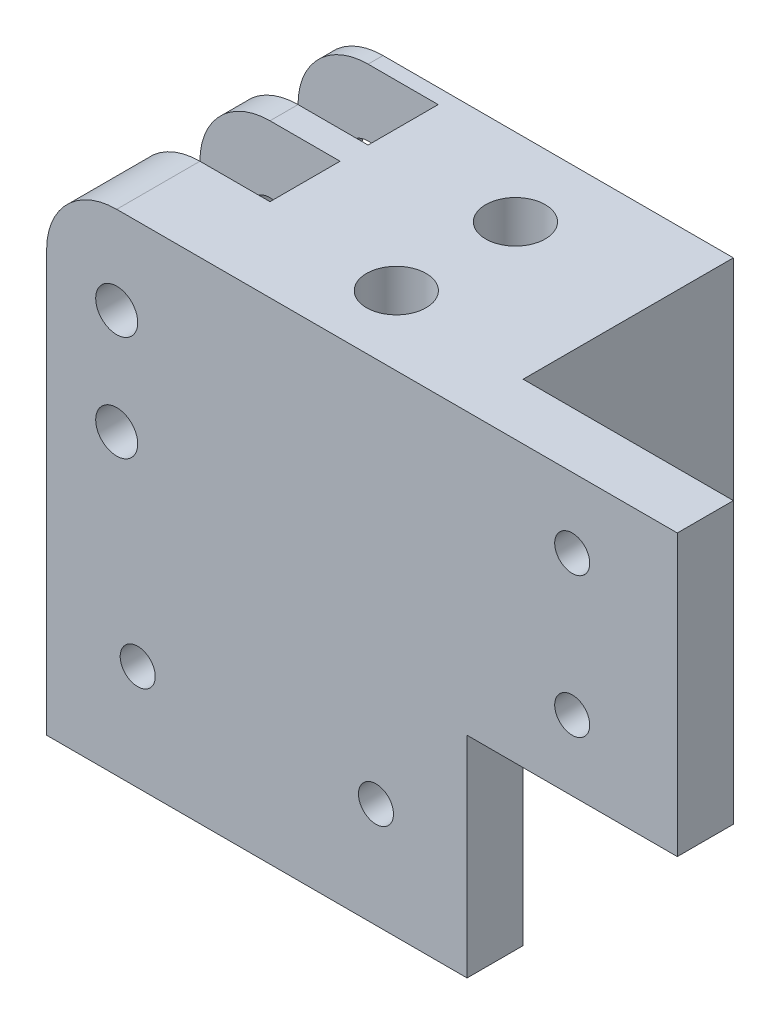
SolidWorks part; units mm, degrees
ref_plane "Front Plane" through (0, 0, 0) normal (0, 0, 1) x (1, 0, 0)
ref_plane "Top Plane" through (0, 0, 0) normal (0, 1, 0) x (1, 0, 0)
ref_plane "Right Plane" through (0, 0, 0) normal (1, 0, 0) x (0, 0, -1)
sketch "Esboço1" plane through (0, 0, 0) normal (0, 0, 1) x (1, 0, 0)
  line L0 (440, 72.2122) -> (440, 102.2122) construction
  line L1 (440, 72.2122) -> (380, 72.2122)
  line L2 (470, 102.2122) -> (470, 142.2122)
  line L3 (470, 142.2122) -> (390, 142.2122)
  line L4 (380, 72.2122) -> (380, 132.2122)
  line L5 (440, 102.2122) -> (470, 102.2122) construction
  line L6 (440, 72.2122) -> (440, 102.2122)
  line L7 (440, 102.2122) -> (470, 102.2122)
  line L9 (440, 87.2122) -> (380, 87.2122) construction
  line L10 (455, 102.2122) -> (455, 142.2122) construction
  arc A0 (390, 142.2122) -> (380, 132.2122) centre (390, 132.2122) ccw
  dimension "D1" = 10
  dimension "D2" = 40
  dimension "D3" = 60
extrude "Ressalto-extrusão1" add sketch "Esboço1" along normal blind 8 contours L4 A0 L3 L2 L7 L6 L1
hole_wizard "Broca de rosquear para tarraxa de M6x1.01" positions "Esboço2" profile "Esboço3" hole size "M6x1.0" standard "Ansi Metric" end condition through all
sketch "Esboço2" plane through (0, 0, 8) normal (0, 0, 1) x (1, 0, 0)
  line L0 (440, 87.2122) -> (380, 87.2122) construction
  line L1 (455, 102.2122) -> (455, 142.2122) construction
  line L2 (380, 72.2122) -> (380, 132.2122) construction
  line L3 (440, 72.2122) -> (440, 102.2122) construction
  line L4 (470, 142.2122) -> (390, 142.2122) construction
  point P0 (393, 87.2122)
  point P4 (427, 87.2122)
  point P6 (455, 112.2122)
  point P10 (455, 132.2122)
  dimension "D1" = 13
  dimension "D2" = 13
  dimension "D3" = 10
  dimension "D4" = 10
sketch "Esboço3" plane through (393, 87.2122, 8) normal (1, 0, 0) x (0, -1, 0)
  line L0 (0, 0) -> (0, 8)
  line L1 (0, 8) -> (2.5, 8)
  line L2 (2.5, 8) -> (2.5, 0)
  line L5 (2.5, 0) -> (0, 0)
  line L11 (0, -6.35) -> (0, 107.95) construction
  dimension "Thru Hole Dia." = 5
  dimension "Thru Hole Depth" = 8
sketch "Esboço4" plane through (0, 0, 0) normal (0, 0, -1) x (-1, 0, 0)
  line L0 (-470, 142.2122) -> (-390, 142.2122) construction
  line L1 (-390, 142.2122) -> (-440, 142.2122)
  line L2 (-380, 132.2122) -> (-380, 102.2122)
  line L3 (-380, 102.2122) -> (-440, 102.2122)
  line L4 (-440, 142.2122) -> (-440, 102.2122)
  line L5 (-380, 72.2122) -> (-380, 132.2122) construction
  arc A0 (-390, 142.2122) -> (-380, 132.2122) centre (-390, 132.2122) cw
  point P11 (-380, 142.2122)
  dimension "D1" = 10
extrude "Ressalto-extrusão2" add sketch "Esboço4" along normal blind 30
sketch "Esboço6" plane through (380, 0, 0) normal (-1, 0, 0) x (0, 0, 1)
  line L0 (-30, 142.2122) -> (0, 142.2122) construction
  line L1 (-27.8749, 102.2122) -> (-17.8749, 102.2122)
  line L2 (-27.8749, 102.2122) -> (-27.8749, 142.2122)
  line L3 (-27.8749, 142.2122) -> (-17.8749, 142.2122)
  line L4 (-17.8749, 102.2122) -> (-17.8749, 142.2122)
  line L5 (-13.8749, 117.2122) -> (-3.8749, 117.2122)
  line L6 (-13.8749, 117.2122) -> (-13.8749, 142.2122)
  line L7 (-13.8749, 142.2122) -> (-3.8749, 142.2122)
  line L8 (-3.8749, 117.2122) -> (-3.8749, 142.2122)
  dimension "D1" = 10
  dimension "D2" = 10
  dimension "D3" = 25
  dimension "D4" = 40
  dimension "D5" = 4
extrude "Corte-extrusão2" cut sketch "Esboço6" against normal blind 20
sketch "Esboço14" plane through (0, 0, -30) normal (0, 0, -1) x (-1, 0, 0)
  circle A2 centre (-390, 129.7122) radius 3
  circle A3 centre (-390, 129.7122) radius 3
  circle A5 centre (-390, 114.7122) radius 3
  circle A6 centre (-390, 114.7122) radius 3
  dimension "D1" = 0.5
  dimension "D2" = 0.5
extrude "Corte-extrusão6" cut sketch "Esboço14" against normal through all
sketch "Esboço15" plane through (0, 142.2122, 0) normal (0, 1, 0) x (1, 0, 0)
  circle A2 centre (420, 18.9024) radius 4.25
  circle A3 centre (420, 18.9024) radius 4.25
  circle A5 centre (420, 1.9024) radius 4.25
  circle A6 centre (420, 1.9024) radius 4.25
  dimension "D1" = 0
  dimension "D2" = 0
extrude "Corte-extrusão7" cut sketch "Esboço15" against normal up to surface (40 mm away) up to face at (400, 102.2122, -18.9374)
